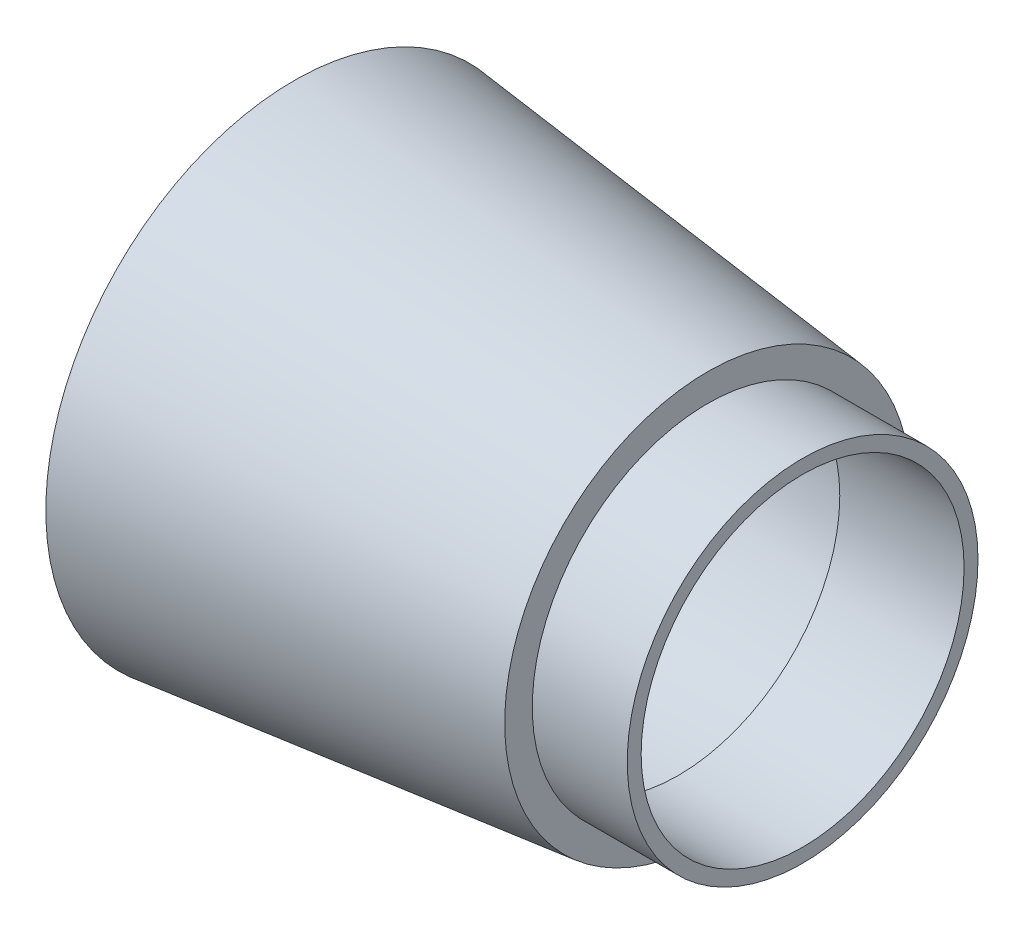
SolidWorks part; units mm, degrees
ref_plane "Front Plane" through (0, 0, 0) normal (0, 0, 1) x (1, 0, 0)
ref_plane "Top Plane" through (0, 0, 0) normal (0, 1, 0) x (1, 0, 0)
ref_plane "Right Plane" through (0, 0, 0) normal (1, 0, 0) x (0, 0, -1)
sketch "Sketch1" plane through (0, 0, 0) normal (0, 0, 1) x (1, 0, 0)
  line L0 (-12.065, 11.43) -> (-12.065, 10.16)
  line L1 (44.7264, 0) -> (-69.8413, 0) construction
  line L2 (6.985, 9.3472) -> (6.985, 8.0772)
  line L3 (-12.065, 0) -> (14.2126, 0) construction
  line L4 (-7.392, 10.9191) -> (-7.392, 0)
  line L5 (6.985, 9.3472) -> (-12.065, 11.43)
  line L6 (-12.065, 10.16) -> (6.985, 8.0772)
  line L7 (-7.392, 0) -> (-2.54, 0)
  line L8 (-2.54, 0) -> (-2.54, 10.3886)
  line L9 (-2.54, 10.3886) -> (-7.392, 10.9191)
  line L11 (11.3259, 7.4362) -> (5.6335, 7.4362)
  line L12 (5.6335, 7.4362) -> (5.6335, 8.225)
  line L13 (5.6335, 8.225) -> (6.985, 8.0772)
  line L14 (6.985, 8.0772) -> (11.3581, 8.0772)
  line L15 (11.3581, 7.4362) -> (11.3259, 7.4362)
  line L16 (11.3581, 8.0772) -> (11.3581, 7.4362)
  dimension "D1" = 19.05
  dimension "D2" = 1.27
  dimension "D3" = 11.43
  dimension "D4" = 9.3472
  dimension "D5" = 1.27
revolve "Revolve4" add sketch "Sketch1" angle 360 about L1 region at (-9.7285, 10.5395, 0) region at (-4.9888, 4.6932, 0) region at (2.2225, 9.2329, 0)
sketch "Sketch2" plane through (-2.54, 0, 0) normal (1, 0, 0) x (0, 0, -1)
  line L3 (-0.3129, 0) -> (0.3129, 0)
  line L4 (-0.3129, 0) -> (-0.3129, 1.0082)
  line L5 (-0.3129, 1.0082) -> (0.3129, 1.0082)
  line L6 (0.3129, 0) -> (0.3129, 1.0082)
  line L9 (-0.3129, 1.0082) -> (0.3129, 1.0082)
  line L10 (-0.3129, 1.0082) -> (-0.3129, 0.7863)
  line L11 (-0.3129, 0.7863) -> (0.3129, 0.7863)
  line L12 (0.3129, 1.0082) -> (0.3129, 0.7863)
  point P3 (0, 0)
  point P8 (0, 0)
revolve "Revolve5" add sketch "Sketch2" angle 180 about L3 region at (-2.54, 0.8972, 0)
